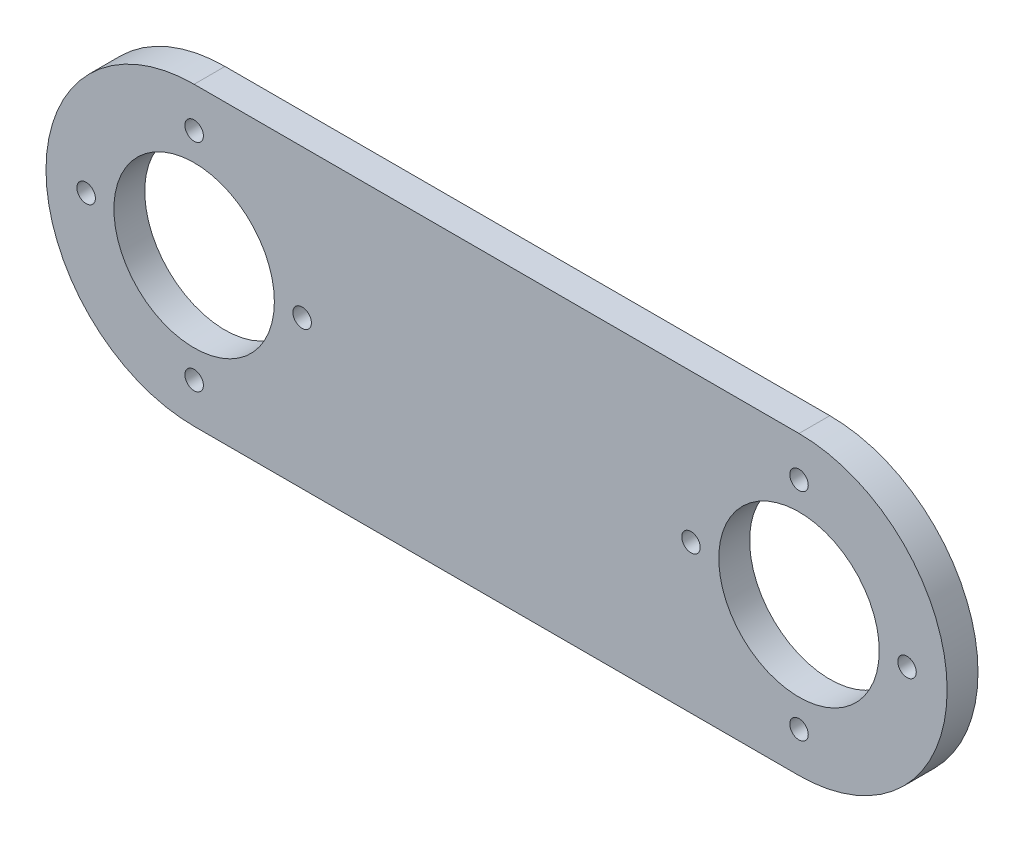
SolidWorks part; units mm, degrees
material "Thornel Mat VMA"
ref_plane "Front Plane" through (0, 0, 0) normal (0, 0, 1) x (1, 0, 0)
ref_plane "Top Plane" through (0, 0, 0) normal (0, 1, 0) x (1, 0, 0)
ref_plane "Right Plane" through (0, 0, 0) normal (1, 0, 0) x (0, 0, -1)
sketch "Sketch1" plane through (0, 0, 0) normal (0, 0, 1) x (1, 0, 0)
  line L0 (-49, 29) -> (49, 29)
  line L1 (-49, -19) -> (49, -19)
  arc A0 (-56.8462, 27.6812) -> (-72.3522, 10.5385) centre (-49, 5) ccw construction
  arc A1 (-49, 29) -> (-49, -19) centre (-49, 5) ccw
  arc A2 (72.9571, 6.434) -> (69.9654, 16.6812) centre (49, 5) ccw construction
  arc A3 (49, -19) -> (49, 29) centre (49, 5) ccw
  arc A4 (49, -14) -> (49, -11) centre (49, -12.5) ccw construction
  arc A5 (66.5, 3.5) -> (66.5, 6.5) centre (66.5, 5) ccw construction
  arc A6 (31.5, 3.5) -> (31.5, 6.5) centre (31.5, 5) ccw construction
  arc A7 (49, 21) -> (49, 24) centre (49, 22.5) ccw construction
  arc A8 (-49, -14) -> (-49, -11) centre (-49, -12.5) ccw construction
  arc A9 (-31.5, 3.5) -> (-31.5, 6.5) centre (-31.5, 5) ccw construction
  arc A10 (-66.5, 3.5) -> (-66.5, 6.5) centre (-66.5, 5) ccw construction
  arc A11 (-49, 24) -> (-49, 21) centre (-49, 22.5) ccw construction
  circle A12 centre (49, -12.5) radius 1.5
  circle A13 centre (66.5, 5) radius 1.5
  circle A14 centre (31.5, 5) radius 1.5
  circle A15 centre (49, 22.5) radius 1.5
  circle A16 centre (-49, -12.5) radius 1.5
  circle A17 centre (-31.5, 5) radius 1.5
  circle A18 centre (-66.5, 5) radius 1.5
  circle A19 centre (-49, 22.5) radius 1.5
  arc A20 (-49, -8) -> (-49, 18) centre (-49, 5) ccw construction
  circle A21 centre (-49, 5) radius 13
  arc A22 (49, -8) -> (49, 18) centre (49, 5) ccw construction
  circle A23 centre (49, 5) radius 13
extrude "Boss-Extrude1" add sketch "Sketch1" along normal blind 5
